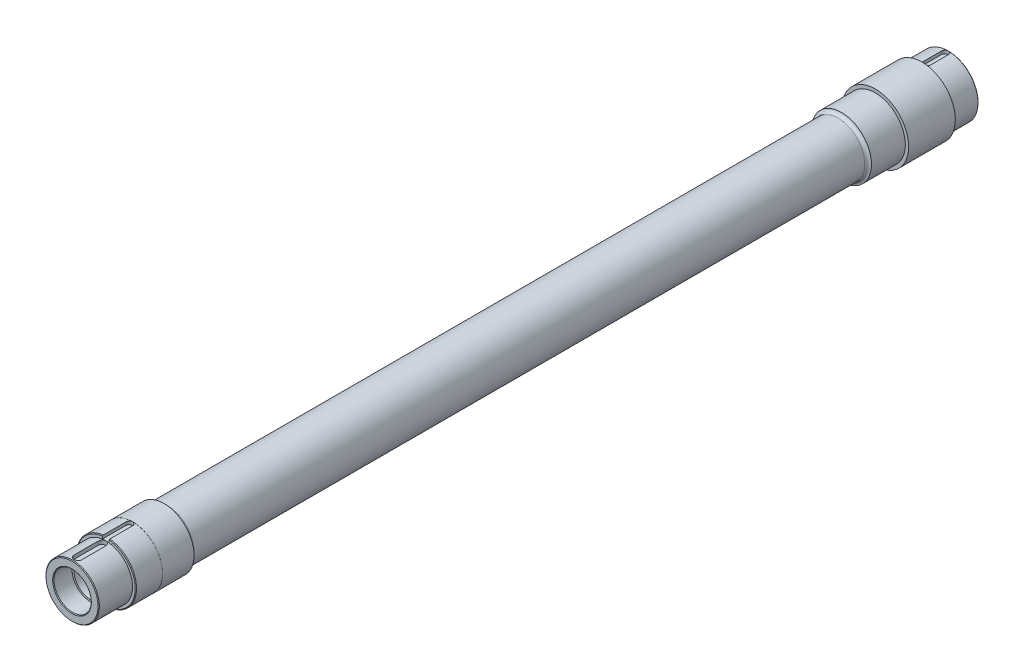
SolidWorks part; units mm, degrees
ref_plane "前视基准面" through (0, 0, 0) normal (0, 0, 1) x (1, 0, 0)
ref_plane "上视基准面" through (0, 0, 0) normal (0, 1, 0) x (1, 0, 0)
ref_plane "右视基准面" through (0, 0, 0) normal (1, 0, 0) x (0, 0, -1)
sketch "草图1" plane through (0, 0, 0) normal (0, 0, 1) x (1, 0, 0)
  circle A0 centre (0, 0) radius 22.5
  circle A1 centre (0, 0) radius 12.5
  dimension "D1" = 45
  dimension "D2" = 25
extrude "拉伸1" add sketch "草图1" along normal blind 659.8
sketch "草图2" plane through (0, 0, 0) normal (0, 0, -1) x (-1, 0, 0)
  circle A0 centre (0, 0) radius 16
  dimension "D1" = 32
extrude "切除-拉伸1" cut sketch "草图2" against normal blind 18
sketch "草图5" plane through (0, 0, 659.8) normal (0, 0, 1) x (1, 0, 0)
  circle A0 centre (0, 0) radius 22.5
  circle A1 centre (0, 0) radius 20
extrude "切除-拉伸3" cut sketch "草图5" against normal blind 604.8
sketch "草图6" plane through (0, 0, 0) normal (0, 0, -1) x (-1, 0, 0)
  circle A0 centre (0, 0) radius 22.5
  circle A1 centre (0, 0) radius 20
extrude "切除-拉伸4" cut sketch "草图6" against normal blind 35
sketch "草图8" plane through (0, 0, 0) normal (0, 0, -1) x (-1, 0, 0)
  circle A0 centre (0, 0) radius 20
  circle A1 centre (0, 0) radius 22.5
extrude "拉伸3" add sketch "草图8" against normal blind 55
sketch "草图9" plane through (0, 0, 659.8) normal (0, 0, 1) x (1, 0, 0)
  circle A0 centre (0, 0) radius 14
  dimension "D1" = 28
extrude "切除-拉伸5" cut sketch "草图9" against normal blind 16.5
sketch "草图10" plane through (0, 0, 659.8) normal (0, 0, 1) x (1, 0, 0)
  circle A0 centre (0, 0) radius 20
  circle A1 centre (0, 0) radius 18
  dimension "D1" = 36
  dimension "D2" = 40
extrude "切除-拉伸6" cut sketch "草图10" against normal blind 22.9
sketch "草图11" plane through (0, 0, 659.8) normal (0, 0, 1) x (1, 0, 0)
  circle A0 centre (0, 0) radius 19
extrude "切除-拉伸7" cut sketch "草图11" against normal blind 2.5
ref_axis "基准轴1" through (0, 0, 643.3) along (0, 0, -1)
ref_plane "基准面1" through (0, 18, 0) normal (0, 1, 0) x (-1, 0, 0)
chamfer "倒角2" distance 0.5 angle 45 1 edges at (14, 0, 657.3)
ref_plane "基准面2" through (0, 0, 588.3) normal (0, 0, 1) x (1, 0, 0)
sketch "草图14" plane through (0, 0, 588.3) normal (0, 0, 1) x (1, 0, 0)
  circle A0 centre (0, 0) radius 22.5
  circle A1 centre (0, 0) radius 20
  dimension "D1" = 40
  dimension "D2" = 45
ref_plane "基准面3" through (0, 22.5, 0) normal (0, 1, 0) x (-1, 0, 0)
sketch "草图15" plane through (0, 22.5, 0) normal (0, 1, 0) x (-1, 0, 0)
  line L0 (-22.5, 0) -> (22.5, 0) construction
  line L1 (-2.5, 16) -> (-2.5, 3)
  line L2 (2.5, 16) -> (2.5, 3)
  arc A0 (-2.5, 3) -> (2.5, 3) centre (0, 3) ccw
  arc A1 (2.5, 16) -> (-2.5, 16) centre (0, 16) ccw
  dimension "D1" = 13
  dimension "D2" = 5
  dimension "D3" = 5
  dimension "D4" = 3
extrude "切除-拉伸11" cut sketch "草图15" against normal blind 2.5
pattern_circular "阵列(圆周)3" count 2 over 360 about axis through (0, 0, 643.3) along (0, 0, -1) of "切除-拉伸11"
sketch "草图18" plane through (0, 0, 55) normal (0, 0, 1) x (1, 0, 0)
  circle A0 centre (0, 0) radius 22.5
  circle A1 centre (0, 0) radius 20
sketch "草图20" plane through (0, 0, 55) normal (0, 0, 1) x (1, 0, 0)
  circle A0 centre (0, 0) radius 25
  circle A1 centre (0, 0) radius 22.5
  dimension "D1" = 50
extrude "拉伸4" add sketch "草图20" against normal blind 35
extrude "拉伸5" add sketch "草图18" along normal blind 25.4
extrude "拉伸6" add sketch "草图14" along normal blind 48.6
sketch "草图21" plane through (0, 0, 636.9) normal (0, 0, 1) x (1, 0, 0)
  circle A0 centre (0, 0) radius 18
  circle A1 centre (0, 0) radius 22.5
  dimension "D1" = 45
extrude "切除-拉伸12" cut sketch "草图21" against normal blind 5
sketch "草图22" plane through (0, 0, 631.9) normal (0, 0, 1) x (1, 0, 0)
  circle A0 centre (0, 0) radius 18
  circle A1 centre (0, 0) radius 20
  dimension "D1" = 40
extrude "拉伸7" add sketch "草图22" along normal blind 25.4
chamfer "倒角3" distance 0.5 angle 45 1 edges at (20, 0, 657.3)
ref_plane "基准面4" through (0, -20, 0) normal (0, 1, 0) x (-1, 0, 0)
sketch "草图23" plane through (0, -20, 0) normal (0, 1, 0) x (-1, 0, 0)
  line L2 (-3, 652.9) -> (-3, 634.9)
  line L3 (3, 652.9) -> (3, 634.9)
  line L4 (20, 631.9) -> (-20, 631.9) construction
  arc A0 (3, 652.9) -> (-3, 652.9) centre (0, 652.9) ccw
  arc A1 (-3, 634.9) -> (3, 634.9) centre (0, 634.9) ccw
  dimension "D1" = 18
  dimension "D2" = 6
  dimension "D3" = 6
  dimension "D4" = 3
extrude "切除-拉伸13" cut sketch "草图23" along normal blind 3
pattern_circular "阵列(圆周)4" count 2 over 360 about axis through (0, 0, 643.3) along (0, 0, -1) of "切除-拉伸13"
sketch "草图24" plane through (0, 0, 0) normal (0, 0, -1) x (-1, 0, 0)
  circle A1 centre (19.5, 0) radius 2
  circle A2 centre (-19.5, 0) radius 2
extrude "切除-拉伸14" cut sketch "草图24" against normal blind 10
chamfer "倒角5" distance 0.5 angle 45 1 edges at (-22.5, 0, 0)
fillet "圆角1" radius 2.5 2 edges at (20, 0, 80.4) (20, 0, 588.3)
sketch "草图25" plane through (0, 0, 631.9) normal (0, 0, 1) x (1, 0, 0)
  circle A0 centre (0, 0) radius 22.5
  circle A1 centre (0, 0) radius 22.45
extrude "切除-拉伸15" cut sketch "草图25" against normal blind 20
chamfer "倒角6" distance 0.5 angle 45 1 edges at (22.45, 0, 631.9)
ref_plane "基准面5" through (0, 22.5, 0) normal (0, 1, 0) x (-1, 0, 0)
sketch "草图26" plane through (0, 22.5, 0) normal (0, 1, 0) x (-1, 0, 0)
  line L0 (22.5, 611.9) -> (-22.5, 611.9) construction
  line L1 (-2.5, 614.4) -> (-2.5, 631.9)
  line L2 (21.95, 631.9) -> (-21.95, 631.9) construction
  line L3 (-2.5, 631.9) -> (2.5, 631.9)
  line L4 (2.5, 631.9) -> (2.5, 614.4)
  arc A0 (-2.5, 614.4) -> (2.5, 614.4) centre (0, 614.4) ccw
  dimension "D1" = 5
  dimension "D2" = 2.5
extrude "切除-拉伸17" cut sketch "草图26" against normal blind 2.5
